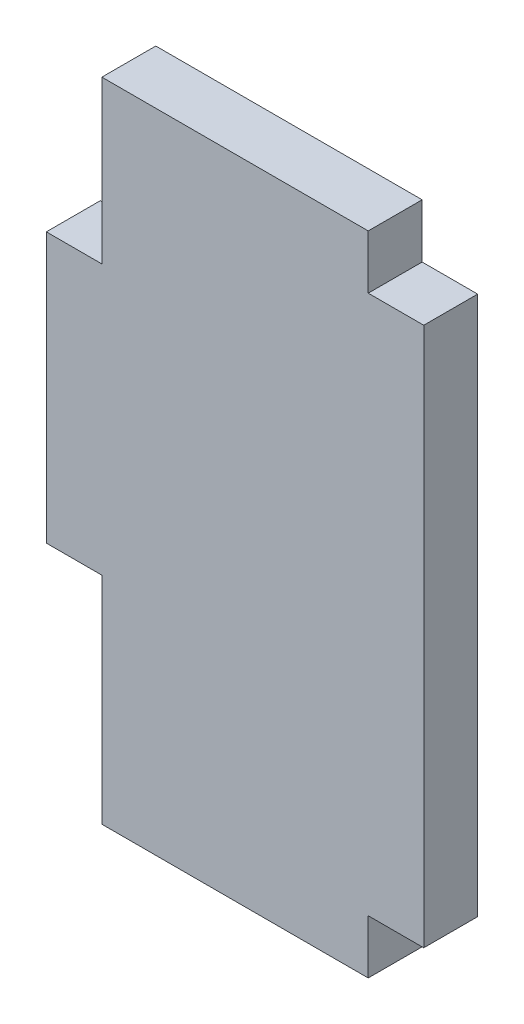
SolidWorks part; units mm, degrees
ref_plane "Front Plane" through (0, 0, 0) normal (0, 0, 1) x (1, 0, 0)
ref_plane "Top Plane" through (0, 0, 0) normal (0, 1, 0) x (1, 0, 0)
ref_plane "Right Plane" through (0, 0, 0) normal (1, 0, 0) x (0, 0, -1)
sketch "Sketch1" plane through (0, 0, 0) normal (0, 0, 1) x (1, 0, 0)
  line L0 (-5.15, 45) -> (0, 45)
  line L2 (-5.15, 45) -> (-5.15, 20)
  line L4 (29.85, 55) -> (29.85, 5)
  line L5 (0, 45) -> (0, 60)
  line L6 (0, 60) -> (24.7, 60)
  line L7 (24.7, 60) -> (24.7, 55)
  line L8 (24.7, 55) -> (29.85, 55)
  line L9 (-5.15, 20) -> (0, 20)
  line L10 (0, 20) -> (0, 0)
  line L11 (0, 0) -> (24.7, 0)
  line L12 (24.7, 0) -> (24.7, 5)
  line L13 (24.7, 5) -> (29.85, 5)
  dimension "D1" = 25
  dimension "D2" = 35
  dimension "D3" = 24.7
  dimension "D4" = 15
  dimension "D5" = 5
  dimension "D6" = 20
  dimension "D7" = 5
extrude "Boss-Extrude1" add sketch "Sketch1" along normal blind 5
